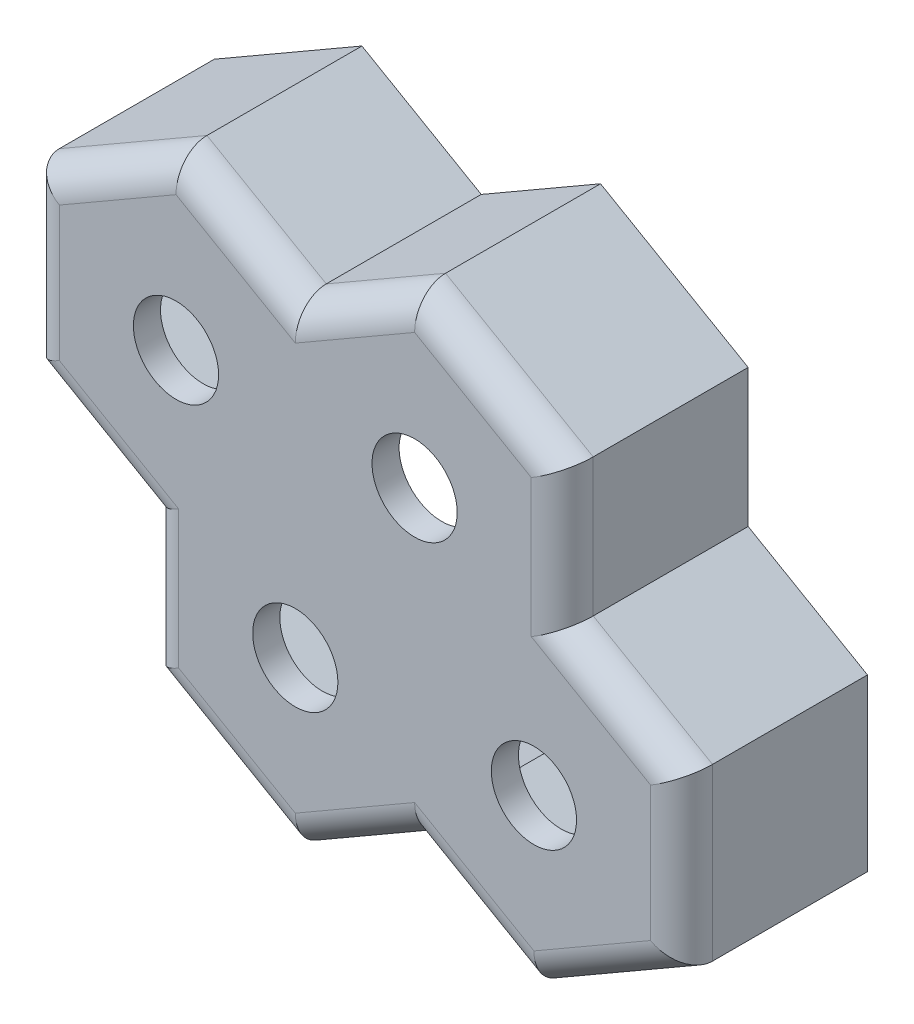
SolidWorks part; units mm, degrees
ref_plane "Ön Düzlem" through (0, 0, 0) normal (0, 0, 1) x (1, 0, 0)
ref_plane "Üst Düzlem" through (0, 0, 0) normal (0, 1, 0) x (1, 0, 0)
ref_plane "Sağ Düzlem" through (0, 0, 0) normal (1, 0, 0) x (0, 0, -1)
sketch "Sketch1" plane through (0, 0, 0) normal (0, 0, 1) x (1, 0, 0)
  line L0 (-24.9263, 5.5) -> (-24.9263, -5.5)
  line L1 (-15.4, 10.134) -> (-24.1763, 5.067)
  line L2 (-24.1763, 5.067) -> (-24.1763, -5.067)
  line L3 (-24.1763, -5.067) -> (-16.4763, -9.5126)
  line L4 (-16.4763, -18.4038) -> (-16.4763, -9.5126)
  line L5 (-7.7, -23.4708) -> (-16.4763, -18.4038)
  line L6 (0, -19.0252) -> (-7.7, -23.4708)
  line L7 (0, -19.0252) -> (7.7, -23.4708)
  line L8 (7.7, -23.4708) -> (16.4763, -18.4038)
  line L9 (16.4763, -18.4038) -> (16.4763, -8.2698)
  line L10 (16.4763, -8.2698) -> (8.7763, -3.8242)
  line L11 (8.7763, 5.067) -> (8.7763, -3.8242)
  line L12 (0, 10.134) -> (8.7763, 5.067)
  line L13 (-7.7, 5.6884) -> (0, 10.134)
  line L14 (-7.7, 5.6884) -> (-15.4, 10.134)
  line L31 (-15.4, 11) -> (-24.9263, 5.5)
  line L32 (-24.9263, -5.5) -> (-17.2263, -9.9456)
  line L33 (-7.7, 6.5544) -> (-15.4, 11)
  line L38 (17.2263, -18.8368) -> (17.2263, -7.8368)
  line L39 (7.7, -24.3368) -> (17.2263, -18.8368)
  line L40 (0, -19.8912) -> (7.7, -24.3368)
  line L41 (17.2263, -7.8368) -> (9.5263, -3.3912)
  line L42 (12.599, -10.5083) -> (12.599, -16.1653)
  line L43 (7.7, -7.6799) -> (12.599, -10.5083)
  line L48 (2.801, -10.5083) -> (7.7, -7.6799)
  line L49 (2.801, -16.1653) -> (2.801, -10.5083)
  line L50 (7.7, -18.9937) -> (2.801, -16.1653)
  line L51 (12.599, -16.1653) -> (7.7, -18.9937)
  line L72 (0, -19.8912) -> (-7.7, -24.3368)
  line L73 (-7.7, -24.3368) -> (-17.2263, -18.8368)
  line L74 (-17.2263, -18.8368) -> (-17.2263, -9.9456)
  line L75 (-7.7, -7.6799) -> (-12.599, -10.5083)
  line L76 (-12.599, -10.5083) -> (-12.599, -16.1653)
  line L77 (-12.599, -16.1653) -> (-7.7, -18.9937)
  line L78 (-7.7, -18.9937) -> (-2.801, -16.1653)
  line L79 (-2.801, -16.1653) -> (-2.801, -10.5083)
  line L80 (-4.899, 2.8285) -> (0, 5.6569)
  line L81 (-4.899, -2.8285) -> (-4.899, 2.8285)
  line L82 (0, -5.6569) -> (-4.899, -2.8285)
  line L83 (4.899, -2.8285) -> (0, -5.6569)
  line L84 (4.899, 2.8285) -> (4.899, -2.8285)
  line L85 (0, 5.6569) -> (4.899, 2.8285)
  line L86 (-20.299, 2.8285) -> (-15.4, 5.6569)
  line L87 (-20.299, -2.8285) -> (-20.299, 2.8285)
  line L88 (-15.4, -5.6569) -> (-20.299, -2.8285)
  line L89 (-10.501, -2.8285) -> (-15.4, -5.6569)
  line L90 (-10.501, 2.8285) -> (-10.501, -2.8285)
  line L91 (-15.4, 5.6569) -> (-10.501, 2.8285)
  line L92 (-2.801, -10.5083) -> (-7.7, -7.6799)
  line L97 (-7.7, 6.5544) -> (0, 11)
  line L98 (9.5263, 5.5) -> (9.5263, -3.3912)
  line L99 (0, 11) -> (9.5263, 5.5)
  circle A0 centre (-15.4, 0) radius 4.899 construction
  circle A1 centre (7.7, -13.3368) radius 4.899 construction
  circle A2 centre (-7.7, -13.3368) radius 4.899 construction
  circle A3 centre (0, 0) radius 4.899 construction
  circle A4 centre (7.7, -13.3368) radius 7.7
  circle A5 centre (-7.7, -13.3368) radius 7.7
  circle A6 centre (-15.4, 0) radius 7.7
  circle A7 centre (0, 0) radius 7.7
  circle A8 centre (-15.4, 0) radius 2.75
  circle A9 centre (0, 0) radius 2.75
  circle A10 centre (-7.7, -13.3368) radius 2.75
  circle A11 centre (7.7, -13.3368) radius 2.75
  circle A12 centre (-15.4, 0) radius 5.6569
  circle A13 centre (0, 0) radius 5.6569
  circle A14 centre (7.7, -13.3368) radius 5.6569
  circle A15 centre (-7.7, -13.3368) radius 5.6569
  dimension "D1" = 0.75
extrude "Boss-Extrude1" add sketch "Sketch1" along normal blind 2 contours L33 L31 L0 L32 L74 L73 L72 L40 L39 L38 L41 L98 L99 L97
extrude "Boss-Extrude2" add sketch "Sketch1<3>" against normal blind 10 contours L99 L97 L33 L31 L0 L32 L74 L73 L72 L40 L39 L38 L41 L98 L1 L14 L13 L12 L11 L10 L9 L8 L7 L6 L5 L4 L3 L2 region at (-19.8881, 7.7736, 0)
sketch "Sketch1<3>" plane through (0, 0, 0) normal (0, 0, 1) x (1, 0, 0) same geometry as "Sketch1"
extrude "Cut-Extrude1" cut sketch "Sketch1<4>" along normal blind 2 contours A8 | A11 | A10 | A9
sketch "Sketch1<4>" plane through (0, 0, 0) normal (0, 0, 1) x (1, 0, 0) same geometry as "Sketch1"
fillet "Fillet1" radius 2 14 edges at (4.7631, 8.25, 2) (9.5263, 1.0544, 2) (13.3763, -5.614, 2) (17.2263, -13.3368, 2) (12.4631, -21.5868, 2) (3.85, -22.114, 2) (-3.85, -22.114, 2) (-12.4631, -21.5868, 2) (-17.2263, -14.3912, 2) (-21.0763, -7.7228, 2) (-24.9263, 0, 2) (-20.1631, 8.25, 2) (-11.55, 8.7772, 2) (-3.85, 8.7772, 2)
extrude "Cut-Extrude5" cut sketch "Sketch1<5>" along normal blind 0.25 contours A12 | A13 | A14 | A15
sketch "Sketch1<5>" plane through (0, 0, 0) normal (0, 0, 1) x (1, 0, 0) same geometry as "Sketch1"
